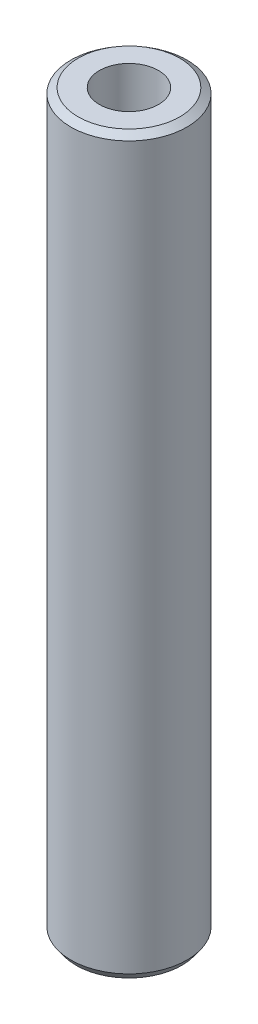
SolidWorks part; units mm, degrees
ref_plane "Front Plane" through (0, 0, 0) normal (0, 0, 1) x (1, 0, 0)
ref_plane "Top Plane" through (0, 0, 0) normal (0, 1, 0) x (1, 0, 0)
ref_plane "Right Plane" through (0, 0, 0) normal (1, 0, 0) x (0, 0, -1)
sketch "Sketch1" plane through (0, 0, 0) normal (0, 1, 0) x (1, 0, 0)
  circle A0 centre (0, 0) radius 47.5
  dimension "SHAFT_OD" = 95
extrude "Boss-Extrude1" add sketch "Sketch1" along normal blind 600
sketch "Sketch2" plane through (0, 0, 0) normal (0, 1, 0) x (1, 0, 0)
  circle A0 centre (0, 0) radius 24.152
  dimension "BORE_D" = 48.3041
extrude "Cut-Extrude1" cut sketch "Sketch2" along normal through all
chamfer "Chamfer1" distance 4.2636 angle 54.262 2 edges at (0, 600, 47.5) (0, 0, 47.5) first distance on face at (0, 600, 47.5) first distance on face at (0, 0, 24.152)
